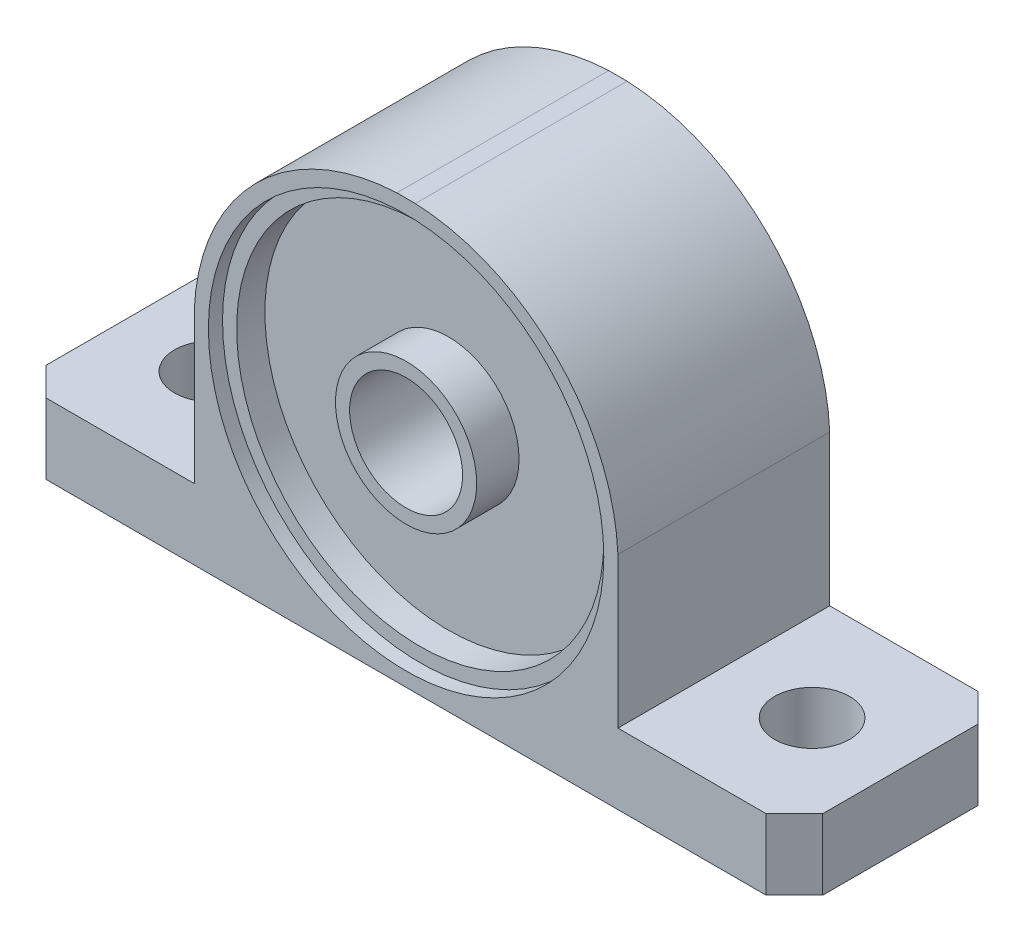
SolidWorks part; units mm, degrees
note: The reader was unsure of these and kept them because the rebuilt part matched: shared geometry of "Sketch3<3>", "Sketch3<4>", "Sketch3<5>", "Sketch5<8>", "Sketch5<9>".
ref_plane "Front Plane" through (0, 0, 0) normal (0, 0, 1) x (1, 0, 0)
ref_plane "Top Plane" through (0, 0, 0) normal (0, 1, 0) x (1, 0, 0)
ref_plane "Right Plane" through (0, 0, 0) normal (1, 0, 0) x (0, 0, -1)
sketch "Sketch1" plane through (0, 0, 0) normal (0, 1, 0) x (1, 0, 0)
  line L0 (25.5, 7.5) -> (27.5, 5.5)
  line L1 (-25.5, 7.5) -> (25.5, 7.5)
  line L2 (-27.5, 5.5) -> (-27.5, -5.5)
  line L3 (-25.5, -7.5) -> (25.5, -7.5)
  line L4 (27.5, 5.5) -> (27.5, -5.5)
  line L5 (-27.5, 7.5) -> (27.5, -7.5) construction
  line L6 (-27.5, -7.5) -> (27.5, 7.5) construction
  line L7 (25.5, -7.5) -> (27.5, -5.5)
  line L8 (-27.5, -5.5) -> (-25.5, -7.5)
  line L9 (-27.5, 5.5) -> (-25.5, 7.5)
  point P0 (0, 0)
extrude "Boss-Extrude1" add sketch "Sketch1" along normal blind 5
sketch "Sketch2" plane through (0, 5, 0) normal (0, 1, 0) x (1, 0, 0)
  line L1 (-15, 7.5) -> (15, 7.5)
  line L2 (-15, 7.5) -> (-15, -7.5)
  line L3 (-15, -7.5) -> (15, -7.5)
  line L4 (15, 7.5) -> (15, -7.5)
  line L5 (-15, 7.5) -> (15, -7.5) construction
  line L6 (-15, -7.5) -> (15, 7.5) construction
  point P0 (0, 0)
  dimension "D1" = 30
  dimension "D2" = 15
extrude "Boss-Extrude2" add sketch "Sketch2" along normal blind 25
sketch "Sketch3" plane through (0, 0, 7.5) normal (0, 0, 1) x (1, 0, 0)
  line L0 (-15, 30) -> (-15, 5) construction
  line L1 (15, 30) -> (15, 5) construction
  line L3 (15, 0) -> (-15, 0)
  line L4 (15, 0) -> (15, 30)
  line L5 (15, 30) -> (-15, 30)
  line L6 (-15, 0) -> (-15, 30)
  line L7 (15, 0) -> (-15, 30) construction
  line L8 (15, 30) -> (-15, 0) construction
  circle A0 centre (0, 15) radius 14
  arc A1 (-15, 15.6528) -> (15, 14.3472) centre (0, 15) cw
  circle A2 centre (0, 15) radius 13
  circle A3 centre (0, 15) radius 5
  circle A4 centre (0, 15) radius 4
  line M5 (15, 5) -> (15, 30)
  line M6 (15, 30) -> (-15, 30)
  line M7 (-15, 30) -> (-15, 5)
  dimension "D1" = 28
  dimension "D3" = 26
  dimension "D4" = 10
  dimension "D5" = 8
  dimension "D2" = 15
extrude "Cut-Extrude1" cut sketch "Sketch3" against normal through all contours A1 M7 M6 | A1 M6 M5
extrude "Cut-Extrude2" cut sketch "Sketch3<3>" against normal blind 1 contours A0 A2
sketch "Sketch3<3>" plane through (0, 0, 7.5) normal (0, 0, 1) x (1, 0, 0) same geometry as "Sketch3"
extrude "Cut-Extrude3" cut sketch "Sketch3<4>" against normal through all both and the other way through all contours A4
sketch "Sketch3<4>" plane through (0, 0, 7.5) normal (0, 0, 1) x (1, 0, 0) same geometry as "Sketch3"
extrude "Cut-Extrude4" cut sketch "Sketch3<5>" against normal blind 3 contours A2 A3
sketch "Sketch3<5>" plane through (0, 0, 7.5) normal (0, 0, 1) x (1, 0, 0) same geometry as "Sketch3"
sketch "Sketch5" plane through (0, 0, -7.5) normal (0, 0, 1) x (1, 0, 0)
  line L3 (15, 0) -> (-15, 0)
  line L4 (15, 0) -> (15, 30)
  line L5 (15, 30) -> (-15, 30)
  line L6 (-15, 0) -> (-15, 30)
  line L7 (15, 0) -> (-15, 30) construction
  line L8 (15, 30) -> (-15, 0) construction
  circle A0 centre (0, 15) radius 14
  arc A1 (-15, 15.6528) -> (15, 14.3472) centre (0, 15) cw
  circle A2 centre (0, 15) radius 13
  circle A3 centre (0, 15) radius 5
  circle A4 centre (0, 15) radius 4
  circle M23 centre (0, 15) radius 4
  dimension "D1" = 28
  dimension "D3" = 26
  dimension "D4" = 10
  dimension "D5" = 8
extrude "Cut-Extrude5" cut sketch "Sketch5" along normal blind 3 contours A2 A3
extrude "Cut-Extrude8" cut sketch "Sketch5<8>" along normal blind 1 contours A0 A2
sketch "Sketch5<8>" plane through (0, 0, -7.5) normal (0, 0, 1) x (1, 0, 0) same geometry as "Sketch5"
extrude "Cut-Extrude9" cut sketch "Sketch5<9>" along normal blind 2 contours A3 M23
sketch "Sketch5<9>" plane through (0, 0, -7.5) normal (0, 0, 1) x (1, 0, 0) same geometry as "Sketch5"
sketch "Sketch6" plane through (0, 5, 0) normal (0, 1, 0) x (1, 0, 0)
  line L0 (-15, 7.5) -> (-15, -7.5) construction
  line L1 (-27.5, 5.5) -> (-27.5, -5.5) construction
  line L3 (0, 0) -> (0, -7.5)
  line L4 (-0.6528, -7.5) -> (0.6528, -7.5) construction
  circle A0 centre (-21.25, 0) radius 2.65
  circle A1 centre (21.25, 0) radius 2.65
  dimension "D1" = 5.3
  dimension "D2" = 6.25
  dimension "D3" = 6.25
extrude "Cut-Extrude10" cut sketch "Sketch6" against normal through all contours A0 | A1
